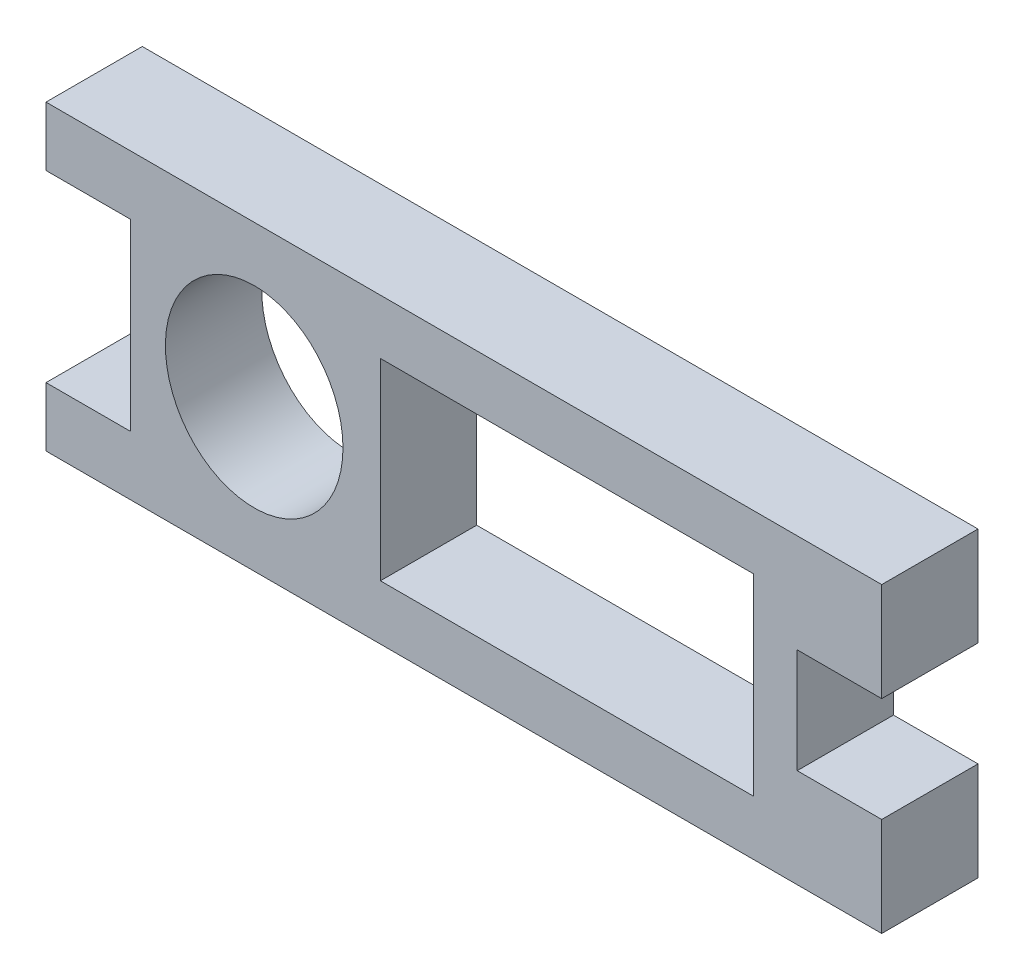
SolidWorks part; units mm, degrees
ref_plane "Front Plane" through (0, 0, 0) normal (0, 0, 1) x (1, 0, 0)
ref_plane "Top Plane" through (0, 0, 0) normal (0, 1, 0) x (1, 0, 0)
ref_plane "Right Plane" through (0, 0, 0) normal (1, 0, 0) x (0, 0, -1)
sketch "Sketch1" plane through (0, 0, 0) normal (0, 0, 1) x (1, 0, 0)
  line L0 (717.4092, 382.5577) -> (717.4092, 393.7158)
  line L1 (738.1592, 380.8428) -> (738.1592, 396.1306) construction
  line L2 (717.4092, 378.9577) -> (757.9092, 378.9577)
  line L3 (755.2592, 382.2867) -> (738.1592, 382.2867)
  line L4 (763.0434, 397.3158) -> (757.9092, 397.3158)
  line L5 (717.4092, 397.3158) -> (757.9092, 397.3158)
  line L6 (763.0434, 384.9577) -> (757.9092, 384.9577)
  line L7 (712.275, 393.7158) -> (717.4092, 393.7158)
  line L8 (763.0434, 378.9577) -> (763.0434, 384.9577)
  line L9 (763.0434, 378.9577) -> (757.9092, 378.9577)
  line L10 (712.275, 397.3158) -> (712.275, 393.7158)
  line L12 (717.4092, 378.9577) -> (712.275, 378.9577)
  line L13 (712.275, 378.9577) -> (712.275, 382.5577)
  line L14 (712.275, 382.5577) -> (717.4092, 382.5577)
  line L15 (717.4092, 397.3158) -> (712.275, 397.3158)
  line L17 (763.0434, 397.3158) -> (763.0434, 391.3158)
  line L18 (763.0434, 391.3158) -> (757.9092, 391.3158)
  line L19 (757.9092, 384.9577) -> (757.9092, 391.3158)
  line L20 (717.4107, 388.1367) -> (-49282.5893, 388.1367) construction
  line L21 (755.2592, 382.2867) -> (755.2592, 393.9867)
  line L22 (738.1592, 382.2867) -> (732.5897, 382.2867)
  line L23 (732.5897, 393.9867) -> (732.5897, 382.2867)
  line L24 (755.2592, 393.9867) -> (738.1592, 393.9867)
  line L25 (738.1592, 393.9867) -> (732.5897, 393.9867)
  line L26 (732.6592, 388.1367) -> (717.4092, 388.1367) construction
  line L31 (732.6592, 390.7223) -> (755.2592, 390.7223) construction
  ellipse E0 centre (724.9224, 388.1367) end of major axis (724.9224, 393.9867) minor radius 5.3936
  point P2 (732.6592, 388.1367)
  point P5 (717.4092, 388.1367)
  point P7 (717.4092, 388.1367)
  point P37 (755.2592, 388.1367)
  point P44 (755.2592, 388.1367)
  point P45 (732.4277, 388.1367)
  dimension "D1" = 11.7
  dimension "D2" = 3.6
  dimension "D3" = 6
  dimension "D4" = 18.3581
  dimension "D5" = 40.5
  dimension "D6" = 5.1342
  dimension "D7" = 22.6695
extrude "Boss-Extrude1" add sketch "Sketch1" along normal blind 5.85 contours L14 L13 L12 L9 L8 region at (717.949, 388.1367, 0)
